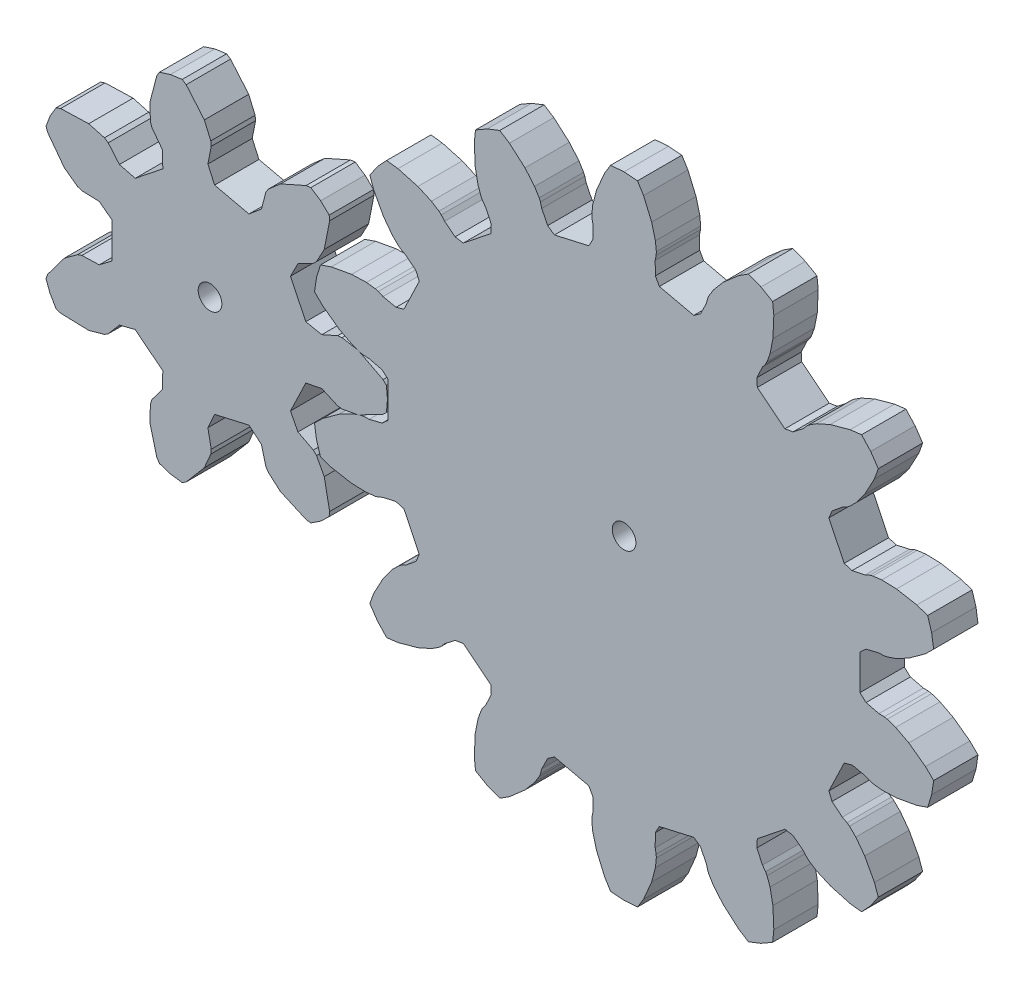
SolidWorks part; units mm, degrees
material "Corrugated Paper"
ref_plane "Front Plane" through (0, 0, 0) normal (0, 0, 1) x (1, 0, 0)
ref_plane "Top Plane" through (0, 0, 0) normal (0, 1, 0) x (1, 0, 0)
ref_plane "Right Plane" through (0, 0, 0) normal (1, 0, 0) x (0, 0, -1)
sketch "Model" plane through (0, 0, 0) normal (0, 0, 1) x (1, 0, 0)
  line L0 (10.824, -15.5893) -> (11.8775, -14.8939)
  line L1 (11.8775, -14.8939) -> (12.7899, -14.0216)
  line L2 (12.7899, -14.0216) -> (12.8434, -13.5144)
  line L3 (12.8434, -13.5144) -> (12.2623, -10.5576)
  line L4 (12.2623, -10.5576) -> (11.4342, -9.0171)
  line L5 (11.4342, -9.0171) -> (11.0892, -8.677)
  line L6 (11.0892, -8.677) -> (9.4401, -7.8202)
  line L7 (9.4401, -7.8202) -> (8.6391, -6.2612)
  line L8 (8.6391, -6.2612) -> (10.2816, -2.8505)
  line L9 (10.2816, -2.8505) -> (11.9999, -2.5047)
  line L10 (11.9999, -2.5047) -> (13.698, -3.2599)
  line L11 (13.698, -3.2599) -> (14.179, -3.3175)
  line L12 (14.179, -3.3175) -> (15.8632, -3.0111)
  line L13 (15.8632, -3.0111) -> (15.2951, -3.2054)
  line L14 (15.2951, -3.2054) -> (13.8858, -3.9376)
  line L15 (13.8858, -3.9376) -> (12.0928, -5.2415)
  line L16 (12.0928, -5.2415) -> (11.2168, -6.1052)
  line L17 (11.2168, -6.1052) -> (11.4324, -7.536)
  line L18 (11.4324, -7.536) -> (11.8589, -8.9187)
  line L19 (11.8589, -8.9187) -> (13.023, -9.3169)
  line L20 (13.023, -9.3169) -> (15.2041, -9.7136)
  line L21 (15.2041, -9.7136) -> (16.7916, -9.7618)
  line L22 (16.7916, -9.7618) -> (17.7443, -9.6477)
  line L23 (17.7443, -9.6477) -> (18.0633, -9.5598)
  line L24 (18.0633, -9.5598) -> (18.5734, -9.3329)
  line L25 (18.5734, -9.3329) -> (19.9687, -9.0348)
  line L26 (19.9687, -9.0348) -> (20.819, -9.2793)
  line L27 (20.819, -9.2793) -> (22.4615, -12.6899)
  line L28 (22.4615, -12.6899) -> (22.1225, -13.5071)
  line L29 (22.1225, -13.5071) -> (21.0194, -14.4122)
  line L30 (21.0194, -14.4122) -> (20.524, -14.6696)
  line L31 (20.524, -14.6696) -> (20.2564, -14.8641)
  line L32 (20.2564, -14.8641) -> (19.5731, -15.5378)
  line L33 (19.5731, -15.5378) -> (18.621, -16.809)
  line L34 (18.621, -16.809) -> (17.5714, -18.7617)
  line L35 (17.5714, -18.7617) -> (17.1569, -19.92)
  line L36 (17.1569, -19.92) -> (17.972, -21.1155)
  line L37 (17.972, -21.1155) -> (18.9562, -22.1762)
  line L38 (18.9562, -22.1762) -> (20.1777, -22.0299)
  line L39 (20.1777, -22.0299) -> (22.3149, -21.441)
  line L40 (22.3149, -21.441) -> (23.7661, -20.7956)
  line L41 (23.7661, -20.7956) -> (24.575, -20.2794)
  line L42 (24.575, -20.2794) -> (24.8242, -20.0619)
  line L43 (24.8242, -20.0619) -> (25.1854, -19.6361)
  line L44 (25.1854, -19.6361) -> (26.3132, -18.7621)
  line L45 (26.3132, -18.7621) -> (27.1854, -18.6134)
  line L46 (27.1854, -18.6134) -> (30.145, -20.9737)
  line L47 (30.145, -20.9737) -> (30.1941, -21.8571)
  line L48 (30.1941, -21.8571) -> (29.593, -23.151)
  line L49 (29.593, -23.151) -> (29.2583, -23.5979)
  line L50 (29.2583, -23.5979) -> (29.1016, -23.8893)
  line L51 (29.1016, -23.8893) -> (28.7783, -24.7928)
  line L52 (28.7783, -24.7928) -> (28.4721, -26.3512)
  line L53 (28.4721, -26.3512) -> (28.3736, -28.5659)
  line L54 (28.3736, -28.5659) -> (28.5027, -29.7893)
  line L55 (28.5027, -29.7893) -> (29.7558, -30.5128)
  line L56 (29.7558, -30.5128) -> (31.1028, -31.0414)
  line L57 (31.1028, -31.0414) -> (32.1398, -30.3796)
  line L58 (32.1398, -30.3796) -> (33.8099, -28.9217)
  line L59 (33.8099, -28.9217) -> (34.8374, -27.7106)
  line L60 (34.8374, -27.7106) -> (35.3421, -26.8946)
  line L61 (35.3421, -26.8946) -> (35.4723, -26.5904)
  line L62 (35.4723, -26.5904) -> (35.613, -26.0501)
  line L63 (35.613, -26.0501) -> (36.2499, -24.7734)
  line L64 (36.2499, -24.7734) -> (36.9712, -24.261)
  line L65 (36.9712, -24.261) -> (40.6618, -25.1033)
  line L66 (40.6618, -25.1033) -> (41.0893, -25.8779)
  line L67 (41.0893, -25.8779) -> (41.1092, -27.3046)
  line L68 (41.1092, -27.3046) -> (41.0015, -27.8524)
  line L69 (41.0015, -27.8524) -> (40.9868, -28.183)
  line L70 (40.9868, -28.183) -> (41.0875, -29.1372)
  line L71 (41.0875, -29.1372) -> (41.4877, -30.6741)
  line L72 (41.4877, -30.6741) -> (42.3599, -32.7123)
  line L73 (42.3599, -32.7123) -> (43.0071, -33.7585)
  line L74 (43.0071, -33.7585) -> (44.45, -33.8667)
  line L75 (44.45, -33.8667) -> (45.8929, -33.7585)
  line L76 (45.8929, -33.7585) -> (46.5401, -32.7123)
  line L77 (46.5401, -32.7123) -> (47.4123, -30.6741)
  line L78 (47.4123, -30.6741) -> (47.8125, -29.1372)
  line L79 (47.8125, -29.1372) -> (47.9132, -28.183)
  line L80 (47.9132, -28.183) -> (47.8985, -27.8524)
  line L81 (47.8985, -27.8524) -> (47.7908, -27.3046)
  line L82 (47.7908, -27.3046) -> (47.8107, -25.8779)
  line L83 (47.8107, -25.8779) -> (48.2382, -25.1033)
  line L84 (48.2382, -25.1033) -> (51.9288, -24.261)
  line L85 (51.9288, -24.261) -> (52.6501, -24.7734)
  line L86 (52.6501, -24.7734) -> (53.287, -26.0501)
  line L87 (53.287, -26.0501) -> (53.4277, -26.5904)
  line L88 (53.4277, -26.5904) -> (53.5579, -26.8946)
  line L89 (53.5579, -26.8946) -> (54.0626, -27.7106)
  line L90 (54.0626, -27.7106) -> (55.0901, -28.9217)
  line L91 (55.0901, -28.9217) -> (56.7602, -30.3796)
  line L92 (56.7602, -30.3796) -> (57.7972, -31.0414)
  line L93 (57.7972, -31.0414) -> (59.1442, -30.5128)
  line L94 (59.1442, -30.5128) -> (60.3973, -29.7893)
  line L95 (60.3973, -29.7893) -> (60.5264, -28.5659)
  line L96 (60.5264, -28.5659) -> (60.4279, -26.3512)
  line L97 (60.4279, -26.3512) -> (60.1217, -24.7928)
  line L98 (60.1217, -24.7928) -> (59.7984, -23.8893)
  line L99 (59.7984, -23.8893) -> (59.6417, -23.5979)
  line L100 (59.6417, -23.5979) -> (59.307, -23.151)
  line L101 (59.307, -23.151) -> (58.7059, -21.8571)
  line L102 (58.7059, -21.8571) -> (58.755, -20.9737)
  line L103 (58.755, -20.9737) -> (61.7146, -18.6134)
  line L104 (61.7146, -18.6134) -> (62.5868, -18.7621)
  line L105 (62.5868, -18.7621) -> (63.7146, -19.6361)
  line L106 (63.7146, -19.6361) -> (64.0758, -20.0619)
  line L107 (64.0758, -20.0619) -> (64.325, -20.2794)
  line L108 (64.325, -20.2794) -> (65.1339, -20.7956)
  line L109 (65.1339, -20.7956) -> (66.5851, -21.441)
  line L110 (66.5851, -21.441) -> (68.7223, -22.0299)
  line L111 (68.7223, -22.0299) -> (69.9438, -22.1762)
  line L112 (69.9438, -22.1762) -> (70.928, -21.1155)
  line L113 (70.928, -21.1155) -> (71.7431, -19.92)
  line L114 (71.7431, -19.92) -> (71.3286, -18.7617)
  line L115 (71.3286, -18.7617) -> (70.279, -16.809)
  line L116 (70.279, -16.809) -> (69.3269, -15.5378)
  line L117 (69.3269, -15.5378) -> (68.6436, -14.8641)
  line L118 (68.6436, -14.8641) -> (68.376, -14.6696)
  line L119 (68.376, -14.6696) -> (67.8806, -14.4122)
  line L120 (67.8806, -14.4122) -> (66.7775, -13.5071)
  line L121 (66.7775, -13.5071) -> (66.4385, -12.6899)
  line L122 (66.4385, -12.6899) -> (68.081, -9.2793)
  line L123 (68.081, -9.2793) -> (68.9313, -9.0348)
  line L124 (68.9313, -9.0348) -> (70.3266, -9.3329)
  line L125 (70.3266, -9.3329) -> (70.8367, -9.5598)
  line L126 (70.8367, -9.5598) -> (71.1557, -9.6477)
  line L127 (71.1557, -9.6477) -> (72.1084, -9.7618)
  line L128 (72.1084, -9.7618) -> (73.6959, -9.7136)
  line L129 (73.6959, -9.7136) -> (75.877, -9.3169)
  line L130 (75.877, -9.3169) -> (77.0411, -8.9187)
  line L131 (77.0411, -8.9187) -> (77.4676, -7.536)
  line L132 (77.4676, -7.536) -> (77.6832, -6.1052)
  line L133 (77.6832, -6.1052) -> (76.8072, -5.2415)
  line L134 (76.8072, -5.2415) -> (75.0142, -3.9376)
  line L135 (75.0142, -3.9376) -> (73.6049, -3.2054)
  line L136 (73.6049, -3.2054) -> (72.697, -2.8949)
  line L137 (72.697, -2.8949) -> (72.3715, -2.8357)
  line L138 (72.3715, -2.8357) -> (71.8134, -2.8188)
  line L139 (71.8134, -2.8188) -> (70.4269, -2.482)
  line L140 (70.4269, -2.482) -> (69.7669, -1.8928)
  line L141 (69.7669, -1.8928) -> (69.7669, 1.8928)
  line L142 (69.7669, 1.8928) -> (70.4269, 2.482)
  line L143 (70.4269, 2.482) -> (71.8134, 2.8188)
  line L144 (71.8134, 2.8188) -> (72.3715, 2.8357)
  line L145 (72.3715, 2.8357) -> (72.697, 2.8949)
  line L146 (72.697, 2.8949) -> (73.6049, 3.2054)
  line L147 (73.6049, 3.2054) -> (75.0142, 3.9376)
  line L148 (75.0142, 3.9376) -> (76.8072, 5.2415)
  line L149 (76.8072, 5.2415) -> (77.6832, 6.1052)
  line L150 (77.6832, 6.1052) -> (77.4676, 7.536)
  line L151 (77.4676, 7.536) -> (77.0411, 8.9187)
  line L152 (77.0411, 8.9187) -> (75.877, 9.3169)
  line L153 (75.877, 9.3169) -> (73.6959, 9.7136)
  line L154 (73.6959, 9.7136) -> (72.1084, 9.7618)
  line L155 (72.1084, 9.7618) -> (71.1557, 9.6477)
  line L156 (71.1557, 9.6477) -> (70.8367, 9.5598)
  line L157 (70.8367, 9.5598) -> (70.3266, 9.3329)
  line L158 (70.3266, 9.3329) -> (68.9313, 9.0348)
  line L159 (68.9313, 9.0348) -> (68.081, 9.2793)
  line L160 (68.081, 9.2793) -> (66.4385, 12.6899)
  line L161 (66.4385, 12.6899) -> (66.7775, 13.5071)
  line L162 (66.7775, 13.5071) -> (67.8806, 14.4122)
  line L163 (67.8806, 14.4122) -> (68.376, 14.6696)
  line L164 (68.376, 14.6696) -> (68.6436, 14.8641)
  line L165 (68.6436, 14.8641) -> (69.3269, 15.5378)
  line L166 (69.3269, 15.5378) -> (70.279, 16.809)
  line L167 (70.279, 16.809) -> (71.3286, 18.7617)
  line L168 (71.3286, 18.7617) -> (71.7431, 19.92)
  line L169 (71.7431, 19.92) -> (70.928, 21.1155)
  line L170 (70.928, 21.1155) -> (69.9438, 22.1762)
  line L171 (69.9438, 22.1762) -> (68.7223, 22.0299)
  line L172 (68.7223, 22.0299) -> (66.5851, 21.441)
  line L173 (66.5851, 21.441) -> (65.1339, 20.7956)
  line L174 (65.1339, 20.7956) -> (64.325, 20.2794)
  line L175 (64.325, 20.2794) -> (64.0758, 20.0619)
  line L176 (64.0758, 20.0619) -> (63.7146, 19.6361)
  line L177 (63.7146, 19.6361) -> (62.5868, 18.7621)
  line L178 (62.5868, 18.7621) -> (61.7146, 18.6134)
  line L179 (61.7146, 18.6134) -> (58.755, 20.9737)
  line L180 (58.755, 20.9737) -> (58.7059, 21.8571)
  line L181 (58.7059, 21.8571) -> (59.307, 23.151)
  line L182 (59.307, 23.151) -> (59.6417, 23.5979)
  line L183 (59.6417, 23.5979) -> (59.7984, 23.8893)
  line L184 (59.7984, 23.8893) -> (60.1217, 24.7928)
  line L185 (60.1217, 24.7928) -> (60.4279, 26.3512)
  line L186 (60.4279, 26.3512) -> (60.5264, 28.5659)
  line L187 (60.5264, 28.5659) -> (60.3973, 29.7893)
  line L188 (60.3973, 29.7893) -> (59.1442, 30.5128)
  line L189 (59.1442, 30.5128) -> (57.7972, 31.0414)
  line L190 (57.7972, 31.0414) -> (56.7602, 30.3796)
  line L191 (56.7602, 30.3796) -> (55.0901, 28.9217)
  line L192 (55.0901, 28.9217) -> (54.0626, 27.7106)
  line L193 (54.0626, 27.7106) -> (53.5579, 26.8946)
  line L194 (53.5579, 26.8946) -> (53.4277, 26.5904)
  line L195 (53.4277, 26.5904) -> (53.287, 26.0501)
  line L196 (53.287, 26.0501) -> (52.6501, 24.7734)
  line L197 (52.6501, 24.7734) -> (51.9288, 24.261)
  line L198 (51.9288, 24.261) -> (48.2382, 25.1033)
  line L199 (48.2382, 25.1033) -> (47.8107, 25.8779)
  line L200 (47.8107, 25.8779) -> (47.7908, 27.3046)
  line L201 (47.7908, 27.3046) -> (47.8985, 27.8524)
  line L202 (47.8985, 27.8524) -> (47.9132, 28.183)
  line L203 (47.9132, 28.183) -> (47.8125, 29.1372)
  line L204 (47.8125, 29.1372) -> (47.4123, 30.6741)
  line L205 (47.4123, 30.6741) -> (46.5401, 32.7123)
  line L206 (46.5401, 32.7123) -> (45.8929, 33.7585)
  line L207 (45.8929, 33.7585) -> (44.45, 33.8667)
  line L208 (44.45, 33.8667) -> (43.0071, 33.7585)
  line L209 (43.0071, 33.7585) -> (42.3599, 32.7123)
  line L210 (42.3599, 32.7123) -> (41.4877, 30.6741)
  line L211 (41.4877, 30.6741) -> (41.0875, 29.1372)
  line L212 (41.0875, 29.1372) -> (40.9868, 28.183)
  line L213 (40.9868, 28.183) -> (41.0015, 27.8524)
  line L214 (41.0015, 27.8524) -> (41.1092, 27.3046)
  line L215 (41.1092, 27.3046) -> (41.0893, 25.8779)
  line L216 (41.0893, 25.8779) -> (40.6618, 25.1033)
  line L217 (40.6618, 25.1033) -> (36.9712, 24.261)
  line L218 (36.9712, 24.261) -> (36.2499, 24.7734)
  line L219 (36.2499, 24.7734) -> (35.613, 26.0501)
  line L220 (35.613, 26.0501) -> (35.4723, 26.5904)
  line L221 (35.4723, 26.5904) -> (35.3421, 26.8946)
  line L222 (35.3421, 26.8946) -> (34.8374, 27.7106)
  line L223 (34.8374, 27.7106) -> (33.8099, 28.9217)
  line L224 (33.8099, 28.9217) -> (32.1398, 30.3796)
  line L225 (32.1398, 30.3796) -> (31.1028, 31.0414)
  line L226 (31.1028, 31.0414) -> (29.7558, 30.5128)
  line L227 (29.7558, 30.5128) -> (28.5027, 29.7893)
  line L228 (28.5027, 29.7893) -> (28.3736, 28.5659)
  line L229 (28.3736, 28.5659) -> (28.4721, 26.3512)
  line L230 (28.4721, 26.3512) -> (28.7783, 24.7928)
  line L231 (28.7783, 24.7928) -> (29.1016, 23.8893)
  line L232 (29.1016, 23.8893) -> (29.2583, 23.5979)
  line L233 (29.2583, 23.5979) -> (29.593, 23.151)
  line L234 (29.593, 23.151) -> (30.1941, 21.8571)
  line L235 (30.1941, 21.8571) -> (30.145, 20.9737)
  line L236 (30.145, 20.9737) -> (27.1854, 18.6134)
  line L237 (27.1854, 18.6134) -> (26.3132, 18.7621)
  line L238 (26.3132, 18.7621) -> (25.1854, 19.6361)
  line L239 (25.1854, 19.6361) -> (24.8242, 20.0619)
  line L240 (24.8242, 20.0619) -> (24.575, 20.2794)
  line L241 (24.575, 20.2794) -> (23.7661, 20.7956)
  line L242 (23.7661, 20.7956) -> (22.3149, 21.441)
  line L243 (22.3149, 21.441) -> (20.1777, 22.0299)
  line L244 (20.1777, 22.0299) -> (18.9562, 22.1762)
  line L245 (18.9562, 22.1762) -> (17.972, 21.1155)
  line L246 (17.972, 21.1155) -> (17.1569, 19.92)
  line L247 (17.1569, 19.92) -> (17.5714, 18.7617)
  line L248 (17.5714, 18.7617) -> (18.621, 16.809)
  line L249 (18.621, 16.809) -> (19.5731, 15.5378)
  line L250 (19.5731, 15.5378) -> (20.2564, 14.8641)
  line L251 (20.2564, 14.8641) -> (20.524, 14.6696)
  line L252 (20.524, 14.6696) -> (21.0194, 14.4122)
  line L253 (21.0194, 14.4122) -> (22.1225, 13.5071)
  line L254 (22.1225, 13.5071) -> (22.4615, 12.6899)
  line L255 (22.4615, 12.6899) -> (20.819, 9.2793)
  line L256 (20.819, 9.2793) -> (19.9687, 9.0348)
  line L257 (19.9687, 9.0348) -> (18.5734, 9.3329)
  line L258 (18.5734, 9.3329) -> (18.0633, 9.5598)
  line L259 (18.0633, 9.5598) -> (17.7443, 9.6477)
  line L260 (17.7443, 9.6477) -> (16.7916, 9.7618)
  line L261 (16.7916, 9.7618) -> (15.2041, 9.7136)
  line L262 (15.2041, 9.7136) -> (13.023, 9.3169)
  line L263 (13.023, 9.3169) -> (11.8589, 8.9187)
  line L264 (11.8589, 8.9187) -> (11.4324, 7.536)
  line L265 (11.4324, 7.536) -> (11.2168, 6.1052)
  line L266 (11.2168, 6.1052) -> (12.0928, 5.2415)
  line L267 (12.0928, 5.2415) -> (13.8858, 3.9376)
  line L268 (13.8858, 3.9376) -> (15.2951, 3.2054)
  line L269 (15.2951, 3.2054) -> (15.8632, 3.0111)
  line L270 (15.8632, 3.0111) -> (14.179, 3.3175)
  line L271 (14.179, 3.3175) -> (13.698, 3.2599)
  line L272 (13.698, 3.2599) -> (11.9999, 2.5047)
  line L273 (11.9999, 2.5047) -> (10.2816, 2.8505)
  line L274 (10.2816, 2.8505) -> (8.6391, 6.2612)
  line L275 (8.6391, 6.2612) -> (9.4401, 7.8202)
  line L276 (9.4401, 7.8202) -> (11.0892, 8.677)
  line L277 (11.0892, 8.677) -> (11.4342, 9.0171)
  line L278 (11.4342, 9.0171) -> (12.2623, 10.5576)
  line L279 (12.2623, 10.5576) -> (12.8434, 13.5144)
  line L280 (12.8434, 13.5144) -> (12.7899, 14.0216)
  line L281 (12.7899, 14.0216) -> (11.8775, 14.8939)
  line L282 (11.8775, 14.8939) -> (10.824, 15.5893)
  line L283 (10.824, 15.5893) -> (10.3177, 15.5286)
  line L284 (10.3177, 15.5286) -> (7.5643, 14.3042)
  line L285 (7.5643, 14.3042) -> (6.2467, 13.154)
  line L286 (6.2467, 13.154) -> (5.9919, 12.742)
  line L287 (5.9919, 12.742) -> (5.5235, 10.9436)
  line L288 (5.5235, 10.9436) -> (4.1818, 9.8158)
  line L289 (4.1818, 9.8158) -> (0.4912, 10.6581)
  line L290 (0.4912, 10.6581) -> (-0.2283, 12.2564)
  line L291 (-0.2283, 12.2564) -> (0.1301, 14.0799)
  line L292 (0.1301, 14.0799) -> (0.0792, 14.5617)
  line L293 (0.0792, 14.5617) -> (-0.6088, 16.1696)
  line L294 (-0.6088, 16.1696) -> (-2.5583, 18.4675)
  line L295 (-2.5583, 18.4675) -> (-2.9881, 18.7418)
  line L296 (-2.9881, 18.7418) -> (-4.239, 18.5724)
  line L297 (-4.239, 18.5724) -> (-5.4396, 18.1823)
  line L298 (-5.4396, 18.1823) -> (-5.7078, 17.7486)
  line L299 (-5.7078, 17.7486) -> (-6.4672, 14.8325)
  line L300 (-6.4672, 14.8325) -> (-6.3895, 13.0853)
  line L301 (-6.3895, 13.0853) -> (-6.2262, 12.6291)
  line L302 (-6.2262, 12.6291) -> (-5.1122, 11.1417)
  line L303 (-5.1122, 11.1417) -> (-5.067, 9.3895)
  line L304 (-5.067, 9.3895) -> (-8.0266, 7.0293)
  line L305 (-8.0266, 7.0293) -> (-9.7248, 7.4633)
  line L306 (-9.7248, 7.4633) -> (-10.927, 8.8804)
  line L307 (-10.927, 8.8804) -> (-11.3354, 9.141)
  line L308 (-11.3354, 9.141) -> (-13.0215, 9.6056)
  line L309 (-13.0215, 9.6056) -> (-16.0335, 9.5141)
  line L310 (-16.0335, 9.5141) -> (-16.516, 9.3491)
  line L311 (-16.516, 9.3491) -> (-17.1635, 8.2655)
  line L312 (-17.1635, 8.2655) -> (-17.607, 7.0837)
  line L313 (-17.607, 7.0837) -> (-17.4352, 6.6035)
  line L314 (-17.4352, 6.6035) -> (-15.6287, 4.1916)
  line L315 (-15.6287, 4.1916) -> (-14.2142, 3.163)
  line L316 (-14.2142, 3.163) -> (-13.7559, 3.0063)
  line L317 (-13.7559, 3.0063) -> (-11.8983, 2.9499)
  line L318 (-11.8983, 2.9499) -> (-10.5002, 1.8928)
  line L319 (-10.5002, 1.8928) -> (-10.5002, -1.8928)
  line L320 (-10.5002, -1.8928) -> (-11.8983, -2.9499)
  line L321 (-11.8983, -2.9499) -> (-13.7559, -3.0063)
  line L322 (-13.7559, -3.0063) -> (-14.2142, -3.163)
  line L323 (-14.2142, -3.163) -> (-15.6287, -4.1916)
  line L324 (-15.6287, -4.1916) -> (-17.4352, -6.6035)
  line L325 (-17.4352, -6.6035) -> (-17.607, -7.0837)
  line L326 (-17.607, -7.0837) -> (-17.1635, -8.2655)
  line L327 (-17.1635, -8.2655) -> (-16.516, -9.3491)
  line L328 (-16.516, -9.3491) -> (-16.0335, -9.5141)
  line L329 (-16.0335, -9.5141) -> (-13.0215, -9.6056)
  line L330 (-13.0215, -9.6056) -> (-11.3354, -9.141)
  line L331 (-11.3354, -9.141) -> (-10.927, -8.8804)
  line L332 (-10.927, -8.8804) -> (-9.7248, -7.4633)
  line L333 (-9.7248, -7.4633) -> (-8.0266, -7.0293)
  line L334 (-8.0266, -7.0293) -> (-5.067, -9.3895)
  line L335 (-5.067, -9.3895) -> (-5.1122, -11.1417)
  line L336 (-5.1122, -11.1417) -> (-6.2262, -12.6291)
  line L337 (-6.2262, -12.6291) -> (-6.3895, -13.0853)
  line L338 (-6.3895, -13.0853) -> (-6.4672, -14.8325)
  line L339 (-6.4672, -14.8325) -> (-5.7078, -17.7486)
  line L340 (-5.7078, -17.7486) -> (-5.4396, -18.1823)
  line L341 (-5.4396, -18.1823) -> (-4.239, -18.5724)
  line L342 (-4.239, -18.5724) -> (-2.9881, -18.7418)
  line L343 (-2.9881, -18.7418) -> (-2.5583, -18.4675)
  line L344 (-2.5583, -18.4675) -> (-0.6088, -16.1696)
  line L345 (-0.6088, -16.1696) -> (0.0792, -14.5617)
  line L346 (0.0792, -14.5617) -> (0.1301, -14.0799)
  line L347 (0.1301, -14.0799) -> (-0.2283, -12.2564)
  line L348 (-0.2283, -12.2564) -> (0.4912, -10.6581)
  line L349 (0.4912, -10.6581) -> (4.1818, -9.8158)
  line L350 (4.1818, -9.8158) -> (5.5235, -10.9436)
  line L351 (5.5235, -10.9436) -> (5.9919, -12.742)
  line L352 (5.9919, -12.742) -> (6.2467, -13.154)
  line L353 (6.2467, -13.154) -> (7.5643, -14.3042)
  line L354 (7.5643, -14.3042) -> (10.3177, -15.5286)
  line L355 (10.3177, -15.5286) -> (10.824, -15.5893)
  line L356 (15.9326, -2.9874) -> (18.5737, -1.6153)
  line L357 (18.5737, -1.6153) -> (18.9368, -1.2572)
  line L358 (18.9368, -1.2572) -> (19.05, 0)
  line L359 (19.05, 0) -> (18.9368, 1.2572)
  line L360 (18.9368, 1.2572) -> (18.5737, 1.6153)
  line L361 (18.5737, 1.6153) -> (15.9326, 2.9874)
  line L362 (15.9326, 2.9874) -> (16.203, 2.8949)
  line L363 (16.203, 2.8949) -> (16.5285, 2.8357)
  line L364 (16.5285, 2.8357) -> (17.0866, 2.8188)
  line L365 (17.0866, 2.8188) -> (18.4731, 2.482)
  line L366 (18.4731, 2.482) -> (19.1331, 1.8928)
  line L367 (19.1331, 1.8928) -> (19.1331, -1.8928)
  line L368 (19.1331, -1.8928) -> (18.4731, -2.482)
  line L369 (18.4731, -2.482) -> (17.0866, -2.8188)
  line L370 (17.0866, -2.8188) -> (16.5285, -2.8357)
  line L371 (16.5285, -2.8357) -> (16.203, -2.8949)
  line L372 (16.203, -2.8949) -> (15.9326, -2.9874)
  line L435 (15.8632, 3.0111) -> (15.9326, 2.9874)
  line L436 (15.9326, -2.9874) -> (15.8632, -3.0111)
  circle A0 centre (0, 0) radius 1.27
  circle A1 centre (44.45, 0) radius 1.27
  point P433 (44.45, 0)
  dimension "D2" = 2.54
  dimension "D3" = 2.54
  dimension "D1" = 44.45
extrude "Boss-Extrude2" add sketch "Model" along normal blind 4.7625 contours L436 L356 L357 L358 L359 L360 L361 L435 L270 L271 L272 L273 L274 L275 L276 L277 L278 L279 L280 L281 L282 L283 L284 L285 L286 L287 L288 L289 L290 L291 L292 L293 L294 L295 L296 L297 L298 L299 L300 L301 L302 L303 L304 L305 L306 L307 L308 L309 L310 L311 L312 region at (10.6332, -15.0384, 0)
extrude "Boss-Extrude3" add sketch "Model<4>" along normal blind 4.7625 separate body contours L372 L436 L13 L14 L15 L16 L17 L18 L19 L20 L21 L22 L23 L24 L25 L26 L27 L28 L29 L30 L31 L32 L33 L34 L35 L36 L37 L38 L39 L40 L41 L42 L43 L44 L45 L46 L47 L48 L49 L50 L51 L52 L53 L54 L55 L56 L57 L58 L59 L60 L61 region at (16.205, -3.8972, 0)
sketch "Model<4>" plane through (0, 0, 0) normal (0, 0, 1) x (1, 0, 0) same geometry as "Model"
equation "\"rodThick\"= 0.1in"
equation "\"thick\"= 3/16in"
equation "\"D1@Boss-Extrude2\"=\"thick\""
equation "\"D1@Boss-Extrude3\"=\"thick\""
